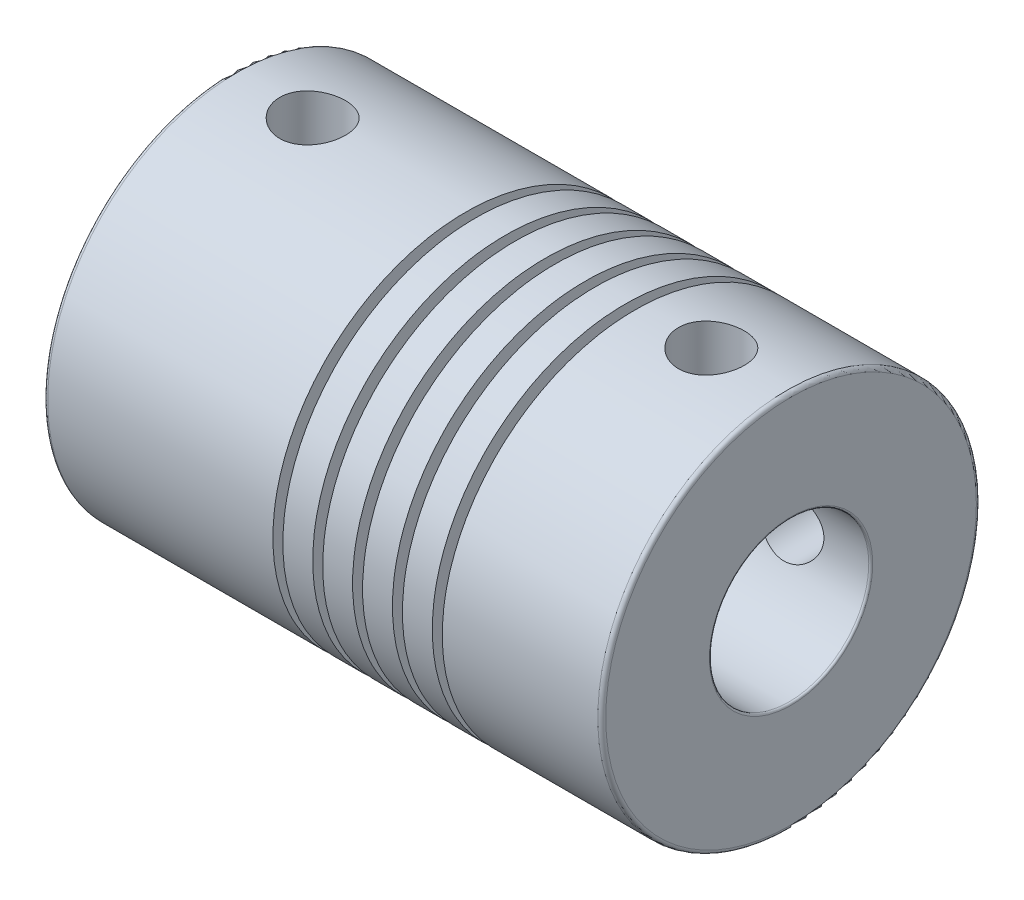
SolidWorks part; units mm, degrees
material "Chrome Stainless Steel"
ref_plane "Front Plane" through (0, 0, 0) normal (0, 0, 1) x (1, 0, 0)
ref_plane "Top Plane" through (0, 0, 0) normal (0, 1, 0) x (1, 0, 0)
ref_plane "Right Plane" through (0, 0, 0) normal (1, 0, 0) x (0, 0, -1)
sketch "Sketch1" plane through (0, 0, 0) normal (1, 0, 0) x (0, 0, -1)
  circle A0 centre (0, 0) radius 9.5
  circle A1 centre (0, 0) radius 2.5
  dimension "D1" = 19
  dimension "D2" = 5
extrude "Boss-Extrude1" add sketch "Sketch1" along normal blind 28 and the other way blind 0.01
sketch "Sketch2" plane through (28, 0, 0) normal (1, 0, 0) x (0, 0, -1)
  circle A0 centre (0, 0) radius 4
  dimension "D1" = 8
extrude "Cut-Extrude1" cut sketch "Sketch2" against normal blind 18 contours A0
sketch "Sketch3" plane through (0, 0, 0) normal (0, 0, 1) x (1, 0, 0)
  line L0 (7.49, 9.5) -> (7.49, -9.5) construction
  line L1 (28, 9.5) -> (-0.01, 9.5) construction
  line L2 (-0.01, -9.5) -> (28, -9.5) construction
  line L3 (20.5, 9.5) -> (20.5, -9.5) construction
  line L4 (-0.01, 9.5) -> (-0.01, -9.5) construction
  line L5 (28, -9.5) -> (28, 9.5) construction
  line L11 (20.5, 9.5) -> (20, 9.5)
  line L12 (20.5, 9.5) -> (20.5, 4)
  line L13 (20.5, 4) -> (20, 4)
  line L14 (20, 9.5) -> (20, 4)
  dimension "D1" = 7.5
  dimension "D2" = 7.5
  dimension "D5" = 0.5
  dimension "D6" = 5.5
ref_plane "Plane4" through (20.59, 0, 0) normal (-1, 0, 0) x (0, 0, 1)
sketch "Sketch7" plane through (20.59, 0, 0) normal (-1, 0, 0) x (0, 0, 1)
  circle A0 centre (0, 0) radius 9.5
  dimension "D1" = 19
curve "Helix/Spiral1" pitch 2 height 10 radius 9.5 left hand yes centre (20.59, 0, 0) axis (-1, 0, 0) start towards (0, 0.7071, -0.7071)
sweep "Cut-Sweep2" cut profiles "Sketch3" path "Helix/Spiral1" align with end faces yes
sketch "Sketch8" plane through (0, 0, 0) normal (0, 0, 1) x (1, 0, 0)
  line L0 (0, 0) -> (28, 0) construction
  line L1 (28, -9.5) -> (28, 9.5) construction
  circle A0 centre (4, 0) radius 1.65
  circle A1 centre (24, 0) radius 1.65
  dimension "D1" = 3.3
  dimension "D2" = 4
  dimension "D3" = 4
extrude "Cut-Extrude3" cut sketch "Sketch8" against normal blind 10
sketch "Sketch10" plane through (0, 0, 0) normal (0, 1, 0) x (1, 0, 0)
  line L0 (-0.01, 0) -> (28, 0) construction
  line L1 (-0.01, 9.5) -> (-0.01, -9.5) construction
  line L2 (28, -9.5) -> (28, 9.5) construction
  circle A0 centre (3.99, 0) radius 1.65
  circle A1 centre (24, 0) radius 1.65
  dimension "D1" = 3.3
  dimension "D2" = 4
  dimension "D3" = 4
extrude "Cut-Extrude4" cut sketch "Sketch10" along normal blind 11
fillet "Fillet1" radius 0.2 2 edges at (-0.01, 0, -9.5) (28, 0, -9.5)
fillet "Fillet2" radius 0.1 2 edges at (-0.01, 0, -2.5) (28, 0, -4)
